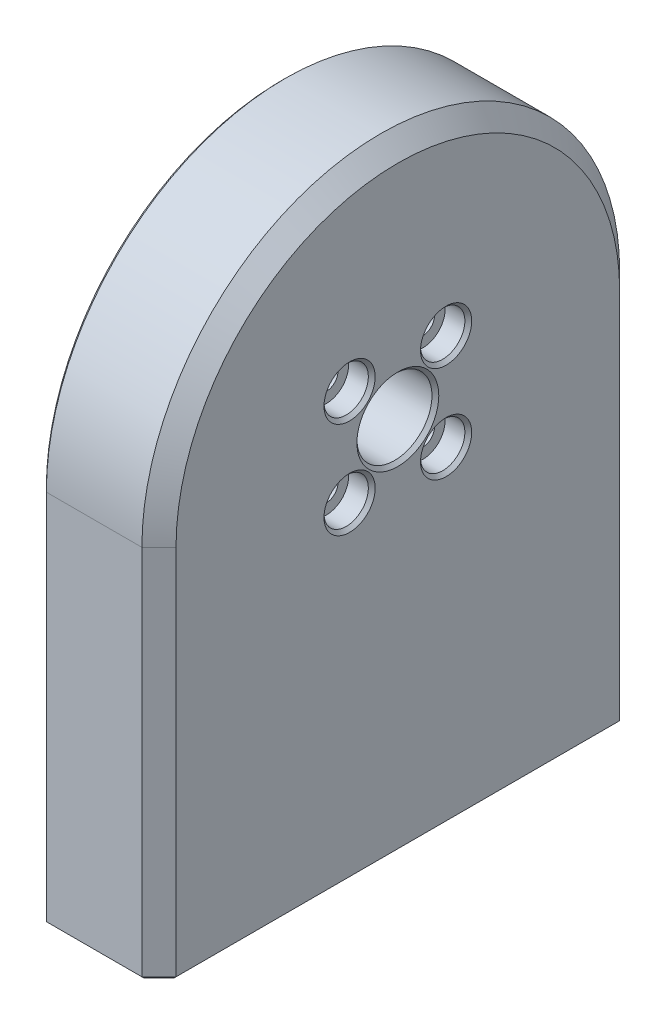
SolidWorks part; units mm, degrees
note: The reader was unsure of these and kept them because the rebuilt part matched: shared geometry of "Sketch1<3>".
ref_plane "Ebene vorne" through (0, 0, 0) normal (0, 0, 1) x (1, 0, 0)
ref_plane "Ebene oben" through (0, 0, 0) normal (0, 1, 0) x (1, 0, 0)
ref_plane "Ebene rechts" through (0, 0, 0) normal (1, 0, 0) x (0, 0, -1)
sketch "Sketch1" plane through (0, 0, 0) normal (1, 0, 0) x (0, 0, -1)
  line L1 (-5.5, 0) -> (5.5, 0)
  line L2 (-35, 0) -> (-35, -55)
  line L3 (-35, -55) -> (35, -55)
  line L4 (35, 0) -> (35, -55)
  circle A0 centre (0, 0) radius 35
  circle A1 centre (0, 0) radius 5.5
  circle A2 centre (0, 0) radius 17
  point P7 (0, -27.5)
  dimension "D1" = 70
  dimension "D3" = 11
  dimension "D4" = 34
  dimension "D2" = 55
extrude "Boss-Extrude1" add sketch "Sketch1" along normal blind 17 contours A0 A1 | A0 L2 L3 L4 | A2 A1
extrude "Boss-Extrude2" add sketch "Sketch1<3>" against normal blind 0.5 contours A2 A1
sketch "Sketch1<3>" plane through (0, 0, 0) normal (1, 0, 0) x (0, 0, -1) same geometry as "Sketch1"
hole_wizard "CBORE for M3 Hex Socket Head Cap Screw1" positions "Sketch2" profile "Sketch3" counterbore size "M3" standard "DIN" end condition through all
sketch "Sketch2" plane through (17, 0, 0) normal (1, 0, 0) x (0, 0, -1)
  line L0 (0, 0) -> (0, 35) construction
  line L2 (0, 0) -> (7.0711, 7.0711) construction
  arc A0 (35, 0) -> (-35, 0) centre (0, 0) ccw construction
  circle A1 centre (0, 0) radius 10
  point P13 (7.0711, 7.0711)
  point P22 (7.0711, -7.0711)
  point P23 (-7.0711, -7.0711)
  point P24 (-7.0711, 7.0711)
  dimension "D1" = 45
  dimension "D2" = 20
  dimension "D3" = 4
sketch "Sketch3" plane through (17, 7.0711, 7.0711) normal (0, 1, 0) x (0, 0, -1)
  line L0 (0, 0) -> (0, 17.5)
  line L1 (0, 17.5) -> (1.7, 17.5)
  line L3 (1.7, 17.5) -> (1.7, 3.4)
  line L4 (1.7, 3.4) -> (3.25, 3.4)
  line L5 (3.25, 3.4) -> (3.25, 0)
  line L7 (3.25, 0) -> (0, 0)
  line L11 (0, -6.35) -> (0, 107.95) construction
  dimension "Thru Hole Dia." = 3.4
  dimension "Thru Hole Depth" = 17.5
  dimension "C'Bore Dia." = 6.5
  dimension "C'Bore Depth" = 3.4
hole_wizard "Ø5.6 (5.6) Diameter Hole1" positions "Sketch4" profile "Sketch5" hole size "Ø5.6" standard "DIN"
sketch "Sketch4" plane through (0, -55, 0) normal (0, -1, 0) x (-1, 0, 0)
  line L0 (-8.5, 35) -> (-8.5, -35) construction
  line L1 (-17, 35) -> (0, 35) construction
  line L2 (-17, -35) -> (0, -35) construction
  point P1 (-8.5, 35)
  point P14 (-8.5, 21.2)
  point P15 (-8.5, 7.4)
  point P16 (-8.5, -6.4)
  point P17 (-8.5, -20.2)
  dimension "D1" = 5
sketch "Sketch5" plane through (8.5, -55, 20.2) normal (1, 0, 0) x (0, 0, -1)
  line L0 (0, 0) -> (0, 9.6824)
  line L1 (0, 9.6824) -> (2.8, 8)
  line L2 (2.8, 8) -> (2.8, 0)
  line L5 (2.8, 0) -> (0, 0)
  line L10 (0, 9.6824) -> (-2.8, 8) construction
  line L11 (0, -6.35) -> (0, 107.95) construction
  dimension "Hole Dia." = 5.6
  dimension "Hole Depth" = 8
  dimension "Drill Angle" = 118
chamfer "2,5mm Chamfer1" distance 2.5 angle 45 3 edges at (17, -27.5, -35) (17, 35, 0) (17, -27.5, 35)
chamfer "0,5mm Chamfer2" distance 0.5 angle 45 22 edges at (8.5, -55, 17.4) (8.5, -55, 3.6) (8.5, -55, -10.2) (8.5, -55, -24) (7.25, -55, 35) (15.75, -55, 33.75) (17, -55, 0) (15.75, -55, -33.75) (7.25, -55, -35) (0, -27.5, 35) (0, -55, 0) (0, -27.5, -35) (0, 35, 0) (-0.5, 7.0711, 5.3711) (-0.5, -7.0711, 5.3711) (-0.5, -7.0711, -8.7711) (-0.5, 7.0711, -8.7711) (17, 7.0711, 3.8211) (17, -7.0711, 3.8211) (17, 7.0711, -10.3211) (17, -7.0711, -10.3211) (17, 0, -5.5)
